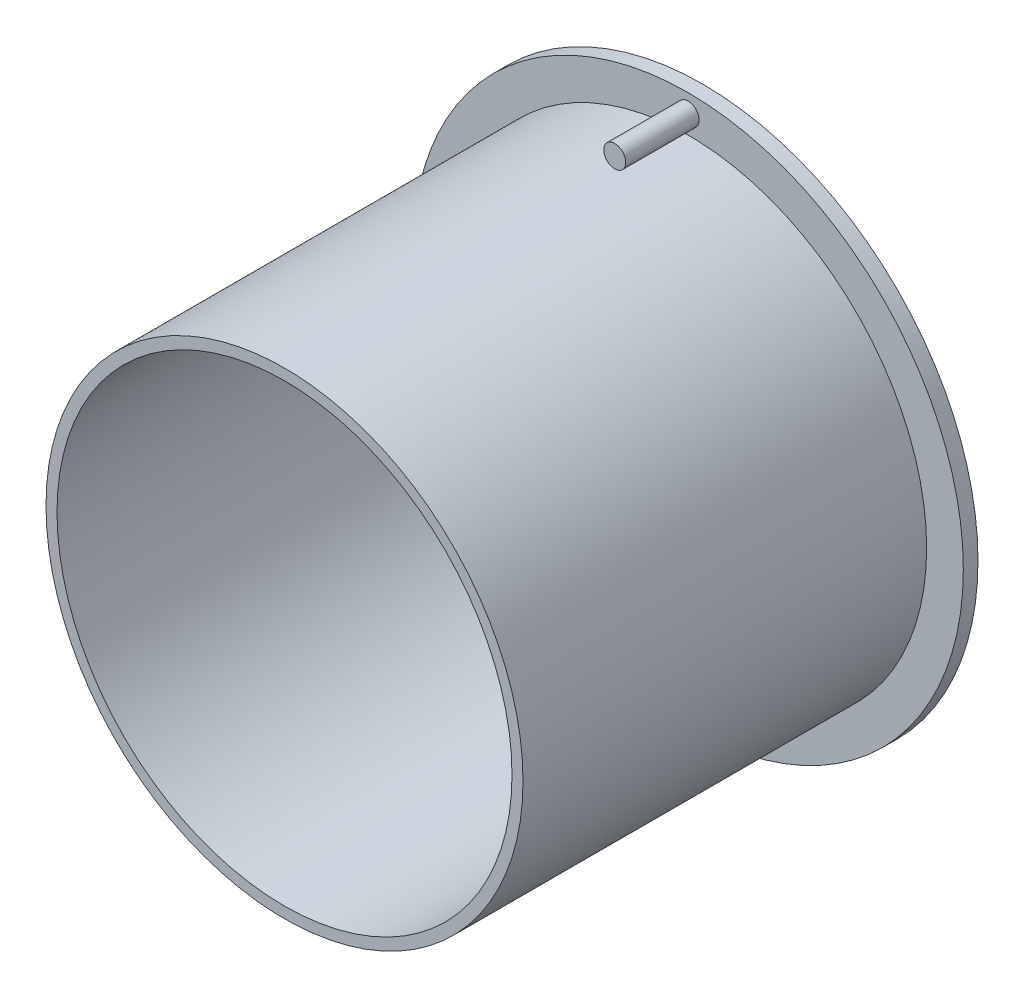
SolidWorks part; units mm, degrees
ref_plane "Front Plane" through (0, 0, 0) normal (0, 0, 1) x (1, 0, 0)
ref_plane "Top Plane" through (0, 0, 0) normal (0, 1, 0) x (1, 0, 0)
ref_plane "Right Plane" through (0, 0, 0) normal (1, 0, 0) x (0, 0, -1)
sketch "Sketch1" plane through (0, 0, 0) normal (0, 0, 1) x (1, 0, 0)
  circle A0 centre (0, 0) radius 37.5
  circle A1 centre (0, 0) radius 32.5
  circle A2 centre (0, 0) radius 31
  dimension "D1" = 75
  dimension "D2" = 65
  dimension "D3" = 62
extrude "Boss-Extrude1" add sketch "Sketch1" against normal blind 2 contours A0 A1 | A1 A2 | A2 region at (-36.4393, 0, 0) region at (-31.5808, 0, 0) region at (0, 0, 0)
sketch "Sketch2" plane through (0, 0, 0) normal (0, 0, 1) x (1, 0, 0)
  circle A0 centre (0, 0) radius 32.5
  circle A1 centre (0, 0) radius 31
  dimension "D1" = 65
  dimension "D2" = 62
extrude "Boss-Extrude2" add sketch "Sketch2" along normal blind 55
sketch "Sketch3" plane through (0, 0, -2) normal (0, 0, -1) x (-1, 0, 0)
  line L0 (0, 37.5) -> (0, 32.5)
  line L1 (0, -32.5) -> (0, -37.5)
  line L2 (0, 37.5) -> (0, 35)
  line L3 (0, 35) -> (6.0304, 35)
  line L4 (0, -35) -> (6.0304, -35)
  circle A0 centre (0, 0) radius 32.5
  circle A3 centre (0, 0) radius 37.5 construction
  point P14 (0, 0)
  dimension "D1" = 65
sketch "Sketch8" plane through (0, 0, 0) normal (0, 0, 1) x (1, 0, 0)
  circle A2 centre (0, 35) radius 1.5
  circle A3 centre (0, -35) radius 1.5
  dimension "D1" = 3
  dimension "D2" = 3
extrude "Boss-Extrude3" add sketch "Sketch8" along normal blind 10
